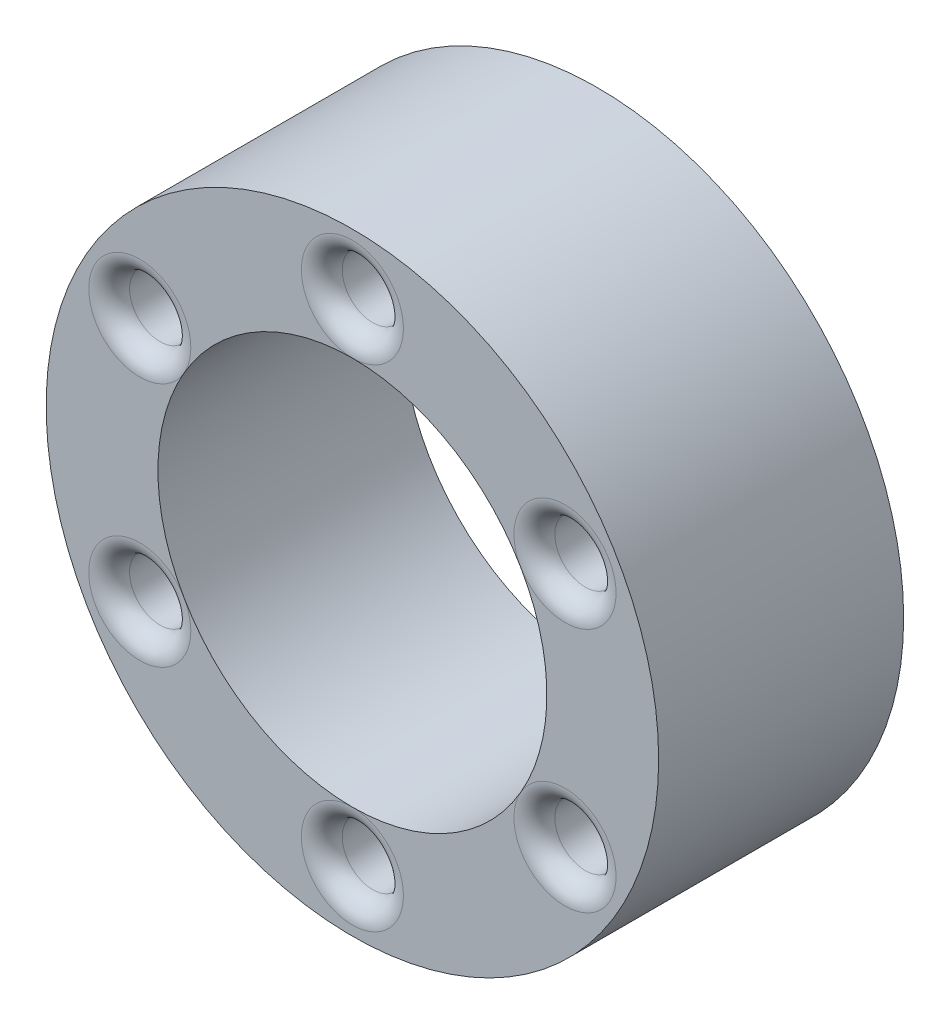
SolidWorks part; units mm, degrees
material "PET"
ref_plane "Front Plane" through (0, 0, 0) normal (0, 0, 1) x (1, 0, 0)
ref_plane "Top Plane" through (0, 0, 0) normal (0, 1, 0) x (1, 0, 0)
ref_plane "Right Plane" through (0, 0, 0) normal (1, 0, 0) x (0, 0, -1)
sketch "Sketch1" plane through (0, 0, 0) normal (0, 0, 1) x (1, 0, 0)
  line L0 (0, 0) -> (0, 2.3813) construction
  line L1 (0, 2.6313) -> (0, 3.0062) construction
  line L2 (0, 2.6313) -> (0, 2.3813) construction
  circle A0 centre (0, 0) radius 2.3813
  circle A1 centre (0, 0) radius 3.75
  circle A2 centre (0, 3.0062) radius 0.375
  circle A3 centre (2.6035, 1.5031) radius 0.375
  circle A4 centre (2.6035, -1.5031) radius 0.375
  circle A5 centre (0, -3.0062) radius 0.375
  circle A6 centre (-2.6035, -1.5031) radius 0.375
  circle A7 centre (-2.6035, 1.5031) radius 0.375
  point P15 (0, 0)
  dimension "D1" = 4.7625
  dimension "D2" = 0.75
  dimension "D4" = 7.5
  dimension "D3" = 0.25
  dimension "D5" = 6
extrude "Boss-Extrude1" add sketch "Sketch1" along normal blind 3
fillet "Fillet6" radius 0.25 12 edges at (-2.2285, -1.5031, 0) (-2.2285, -1.5031, 3) (0.375, -3.0062, 0) (0.375, -3.0062, 3) (2.9785, -1.5031, 0) (2.9785, -1.5031, 3) (2.9785, 1.5031, 0) (2.9785, 1.5031, 3) (0.375, 3.0062, 0) (0.375, 3.0062, 3) (-2.2285, 1.5031, 0) (-2.2285, 1.5031, 3)
